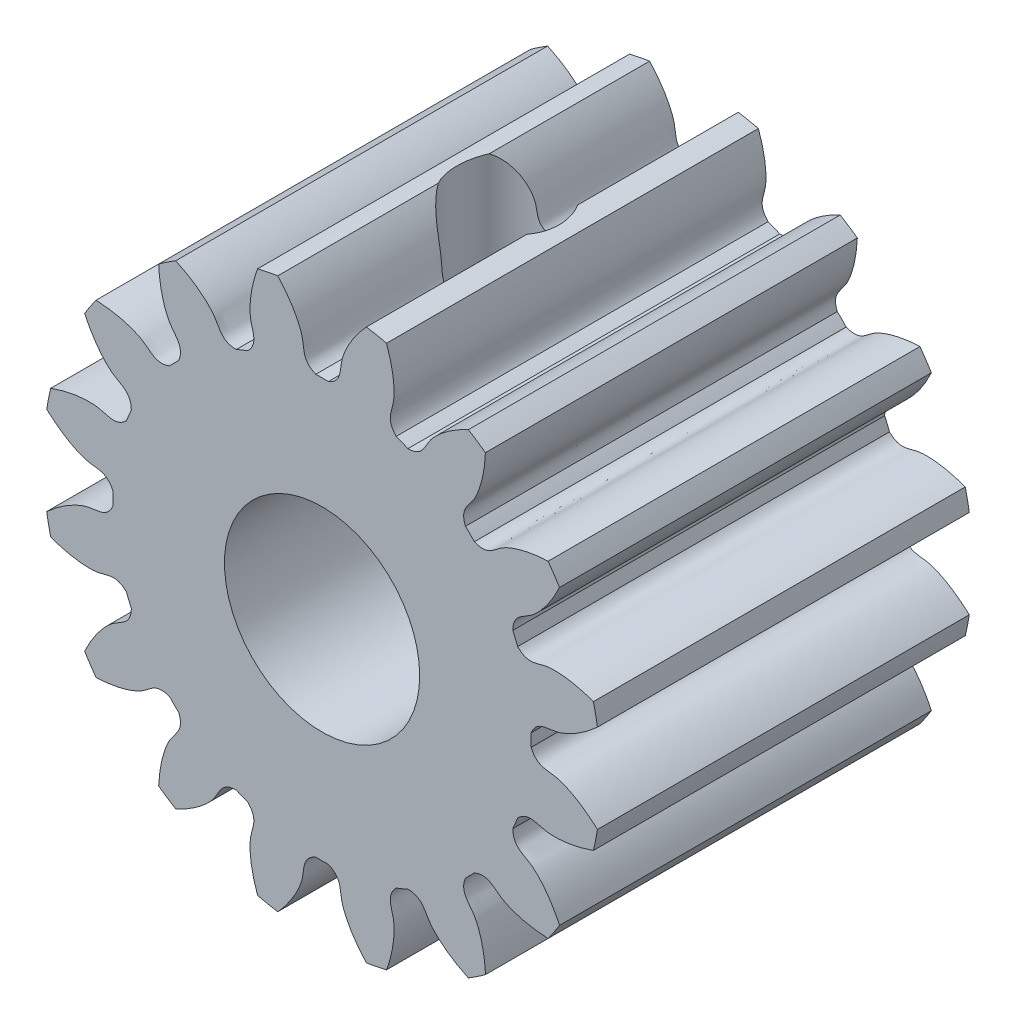
SolidWorks part; units mm, degrees
ref_plane "前视基准面" through (0, 0, 0) normal (0, 0, 1) x (1, 0, 0)
ref_plane "上视基准面" through (0, 0, 0) normal (0, 1, 0) x (1, 0, 0)
ref_plane "右视基准面" through (0, 0, 0) normal (1, 0, 0) x (0, 0, -1)
other "Configuration Table"
sketch "草图1" plane through (0, 0, 0) normal (0, 0, 1) x (1, 0, 0)
  circle A0 centre (0, 0) radius 4.5
extrude "凸台-拉伸1" add sketch "草图1" along normal blind 6
ref_axis "基准轴1" through (0, 0, 6) along (0, 0, -1)
sketch "草图2" plane through (0, 0, 0) normal (0, 0, 1) x (1, 0, 0)
  line L0 (0, 0) -> (0, 4.5) construction
  circle A0 centre (0, 0) radius 4.5 construction
  arc A1 (0.1017, 3.3735) -> (-0.1017, 3.3735) centre (0, 0) ccw
  arc A2 (1.5609, 5.0814) -> (-1.5609, 5.0814) centre (0, 0) ccw
  spline S0 degree 3 poles (0.1017, 3.3735) (0.3209, 3.4651) (0.2847, 3.6353) (0.3224, 3.7934) (0.3256, 3.8058) (0.3295, 3.8195) (0.334, 3.8346) (0.3394, 3.8511) (0.3455, 3.8688) (0.3526, 3.8879) (0.3605, 3.9082) (0.3695, 3.9297) (0.3794, 3.9524) (0.3905, 3.9763) (0.4027, 4.0013) (0.4161, 4.0274) (0.4307, 4.0545) (0.4466, 4.0827) (0.4638, 4.1118) (0.4823, 4.1419) (0.5023, 4.1728) (0.5238, 4.2046) (0.5467, 4.2372) (0.5712, 4.2705) (0.5973, 4.3045) (0.6249, 4.3392) (0.6543, 4.3744) (0.6853, 4.4102) (0.718, 4.4465) (0.7524, 4.4833) (0.7887, 4.5204) (0.8267, 4.5578) (0.8666, 4.5955) (0.9084, 4.6334) (0.952, 4.6715) (0.9975, 4.7096) (1.045, 4.7478) (1.0944, 4.7859) (1.1457, 4.8239) (1.1991, 4.8618) (1.2544, 4.8994) (1.3117, 4.9367) (1.3711, 4.9737) (1.4537, 5.023) (1.5175, 5.0584) (1.5609, 5.0814) knots 0 0 0 0 0.200958 0.205848 0.21139 0.217584 0.224431 0.231929 0.240079 0.248881 0.258335 0.268441 0.2792 0.29061 0.302672 0.315386 0.328753 0.342771 0.357441 0.372764 0.388738 0.405364 0.422643 0.440573 0.459155 0.47839 0.498276 0.518814 0.540005 0.561847 0.584342 0.607488 0.631287 0.655737 0.68084 0.706594 0.733001 0.760059 0.78777 0.816132 0.845147 0.874814 0.905132 0.936103 1 1 1 1
  spline S1 degree 3 poles (-0.1017, 3.3735) (-0.3209, 3.4651) (-0.2847, 3.6353) (-0.3224, 3.7934) (-0.3256, 3.8058) (-0.3295, 3.8195) (-0.334, 3.8346) (-0.3394, 3.8511) (-0.3455, 3.8688) (-0.3526, 3.8879) (-0.3605, 3.9082) (-0.3695, 3.9297) (-0.3794, 3.9524) (-0.3905, 3.9763) (-0.4027, 4.0013) (-0.4161, 4.0274) (-0.4307, 4.0545) (-0.4466, 4.0827) (-0.4638, 4.1118) (-0.4823, 4.1419) (-0.5023, 4.1728) (-0.5238, 4.2046) (-0.5467, 4.2372) (-0.5712, 4.2705) (-0.5973, 4.3045) (-0.6249, 4.3392) (-0.6543, 4.3744) (-0.6853, 4.4102) (-0.718, 4.4465) (-0.7524, 4.4833) (-0.7887, 4.5204) (-0.8267, 4.5578) (-0.8666, 4.5955) (-0.9084, 4.6334) (-0.952, 4.6715) (-0.9975, 4.7096) (-1.045, 4.7478) (-1.0944, 4.7859) (-1.1457, 4.8239) (-1.1991, 4.8618) (-1.2544, 4.8994) (-1.3117, 4.9367) (-1.3711, 4.9737) (-1.4537, 5.023) (-1.5175, 5.0584) (-1.5609, 5.0814) knots 0 0 0 0 0.200958 0.205848 0.21139 0.217584 0.224431 0.231929 0.240079 0.248881 0.258335 0.268441 0.2792 0.29061 0.302672 0.315386 0.328753 0.342771 0.357441 0.372764 0.388738 0.405364 0.422643 0.440573 0.459155 0.47839 0.498276 0.518814 0.540005 0.561847 0.584342 0.607488 0.631287 0.655737 0.68084 0.706594 0.733001 0.760059 0.78777 0.816132 0.845147 0.874814 0.905132 0.936103 1 1 1 1
extrude "切除-拉伸1" cut sketch "草图2" along normal through all
pattern_circular "阵列(圆周)1" count 16 every 22.5 about axis through (0, 0, 6) along (0, 0, -1) of "切除-拉伸1"
sketch "草图3" plane through (0, 0, 0) normal (0, 0, 1) x (1, 0, 0)
  circle A0 centre (0, 0) radius 4 construction
  dimension "Dn" = 8
sketch "草图4" plane through (0, 0, 6) normal (0, 0, 1) x (1, 0, 0)
  circle A0 centre (0, 0) radius 1.575
  dimension "D1" = 3.15
extrude "切除-拉伸2" cut sketch "草图4" against normal blind 10
sketch "草图5" plane through (0, 0, 0) normal (0, 1, 0) x (1, 0, 0)
  line L0 (0, 0) -> (0, -6) construction
  line L1 (-0.1017, -6) -> (0.1017, -6) construction
  circle A0 centre (0, -3) radius 0.825
  dimension "D1" = 1.65
extrude "切除-拉伸3" cut sketch "草图5" along normal up to next
